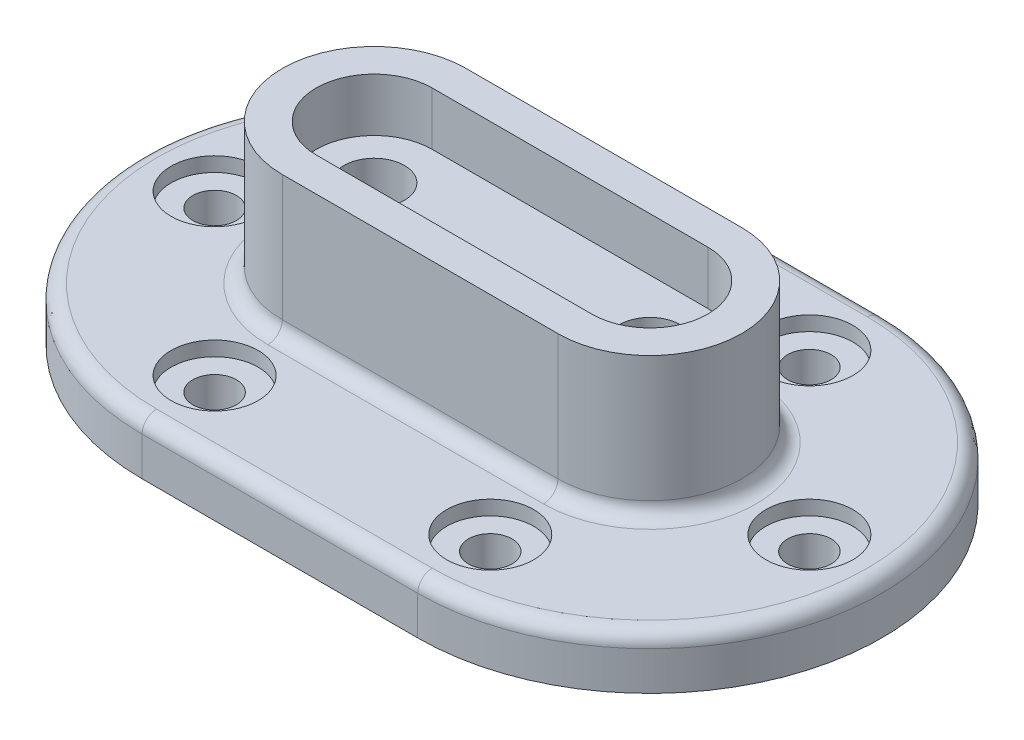
SolidWorks part; units mm, degrees
ref_plane "정면" through (0, 0, 0) normal (0, 0, 1) x (1, 0, 0)
ref_plane "윗면" through (0, 0, 0) normal (0, 1, 0) x (1, 0, 0)
ref_plane "우측면" through (0, 0, 0) normal (1, 0, 0) x (0, 0, -1)
sketch "스케치1" plane through (0, 0, 0) normal (0, 1, 0) x (1, 0, 0)
  line L0 (0, 0) -> (138.7655, 0) construction
  line L1 (33.7655, 45.9301) -> (33.7655, -48.2366) construction
  line L2 (90.7655, 45.9301) -> (90.7655, -48.2366) construction
  line L3 (33.7655, 0) -> (90.7655, 0) construction
  line L4 (33.7655, 48) -> (90.7655, 48)
  line L5 (33.7655, -48) -> (90.7655, -48)
  line L6 (33.7655, 0) -> (90.7655, 0) construction
  line L7 (33.7655, 33) -> (90.7655, 33) construction
  line L8 (33.7655, -33) -> (90.7655, -33) construction
  line L9 (33.7655, 0) -> (90.7655, 0) construction
  line L10 (33.7655, 19) -> (90.7655, 19)
  line L11 (33.7655, -19) -> (90.7655, -19)
  line L12 (33.7655, 0) -> (90.7655, 0) construction
  line L13 (33.7655, 12) -> (90.7655, 12)
  line L14 (33.7655, -12) -> (90.7655, -12)
  arc A0 (33.7655, 48) -> (33.7655, -48) centre (33.7655, 0) ccw
  arc A1 (90.7655, -48) -> (90.7655, 48) centre (90.7655, 0) ccw
  arc A2 (33.7655, 33) -> (33.7655, -33) centre (33.7655, 0) ccw construction
  arc A3 (90.7655, -33) -> (90.7655, 33) centre (90.7655, 0) ccw construction
  arc A4 (33.7655, 19) -> (33.7655, -19) centre (33.7655, 0) ccw
  arc A5 (90.7655, -19) -> (90.7655, 19) centre (90.7655, 0) ccw
  arc A6 (33.7655, 12) -> (33.7655, -12) centre (33.7655, 0) ccw
  arc A7 (90.7655, -12) -> (90.7655, 12) centre (90.7655, 0) ccw
  point P9 (62.2655, 0)
  point P14 (-14.2345, 0)
  point P17 (62.2655, 0)
  point P22 (62.2655, 0)
  point P31 (62.2655, 0)
  dimension "D3" = 48
  dimension "D4" = 33
  dimension "D5" = 19
  dimension "D6" = 12
  dimension "D1" = 57
  dimension "D2" = 153
extrude "보스-돌출1" add sketch "스케치1" along normal blind 11 contours L4 A1 L5 A0
sketch "스케치2" plane through (0, 11, 0) normal (0, 1, 0) x (1, 0, 0)
  arc A0 (90.7655, -33) -> (90.7655, 33) centre (90.7655, 0) ccw construction
  arc A1 (33.7655, 33) -> (33.7655, -33) centre (33.7655, 0) ccw construction
  point P0 (33.7655, 33)
  point P1 (90.7655, 33)
  point P3 (123.7655, 0)
  point P5 (90.7655, -33)
  point P9 (33.7655, -33)
  point P11 (0.7655, 0)
  point P13 (-36.6843, 40.0158)
sketch "스케치4" plane through (0, 11, 0) normal (0, 1, 0) x (1, 0, 0)
  circle A0 centre (33.7655, 33) radius 9
  circle A1 centre (33.7655, 33) radius 4.5
  circle A2 centre (90.7655, 33) radius 9
  circle A3 centre (90.7655, 33) radius 4.5
  circle A4 centre (123.7655, 0) radius 9
  circle A5 centre (123.7655, 0) radius 4.5
  circle A6 centre (90.7655, -33) radius 9
  circle A7 centre (90.7655, -33) radius 4.5
  circle A8 centre (33.7655, -33) radius 9
  circle A9 centre (33.7655, -33) radius 4.5
  circle A10 centre (0.7655, 0) radius 9
  circle A11 centre (0.7655, 0) radius 4.5
extrude "컷-돌출1" cut sketch "스케치4" against normal blind 3 contours A10 A11 | A0 A1 | A2 A3 | A4 A5 | A6 A7 | A8 A9 region at (25.02, 11, -33) region at (82.02, 11, -33) region at (115.02, 11, 0) region at (82.02, 11, 33) region at (25.02, 11, 33) region at (-7.98, 11, 0)
extrude "컷-돌출2" cut sketch "스케치4<3>" against normal blind 11 contours A9 | A11 | A1 | A3 | A5 | A7 region at (33.7655, 11, -33) region at (90.7655, 11, -33) region at (123.7655, 11, 0) region at (90.7655, 11, 33) region at (33.7655, 11, 33) region at (0.7655, 11, 0)
sketch "스케치4<3>" plane through (0, 11, 0) normal (0, 1, 0) x (1, 0, 0) same geometry as "스케치4"
extrude "보스-돌출3" add sketch "스케치1<5>" along normal blind 40 contours L11 A5 L10 A4 A7 L14 A6 L13 region at (62.2655, 0, -17.9768)
sketch "스케치1<5>" plane through (0, 0, 0) normal (0, 1, 0) x (1, 0, 0) same geometry as "스케치1"
extrude "보스-돌출4" add sketch "스케치1<6>" along normal blind 29 contours L14 A7 L13 A6 region at (62.2655, 0, 0)
sketch "스케치1<6>" plane through (0, 0, 0) normal (0, 1, 0) x (1, 0, 0) same geometry as "스케치1"
sketch "스케치7" plane through (0, 29, 0) normal (0, 1, 0) x (1, 0, 0)
  point P0 (33.7655, 0)
  point P1 (90.7655, 0)
sketch "스케치8" plane through (0, 29, 0) normal (0, 1, 0) x (1, 0, 0)
  circle A0 centre (33.7655, 0) radius 6.25
  circle A1 centre (90.7655, 0) radius 6.25
extrude "컷-돌출3" cut sketch "스케치8" against normal through all contours A0 | A1 region at (33.7655, 29, 0) region at (90.7655, 29, 0)
fillet "필렛1" radius 3 4 edges at (-14.2345, 11, 0) (62.2655, 11, -48) (138.7655, 11, 0) (62.2655, 11, 48)
fillet "필렛2" radius 3 4 edges at (62.2655, 11, -19) (14.7655, 11, 0) (109.7655, 11, 0) (62.2655, 11, 19)
